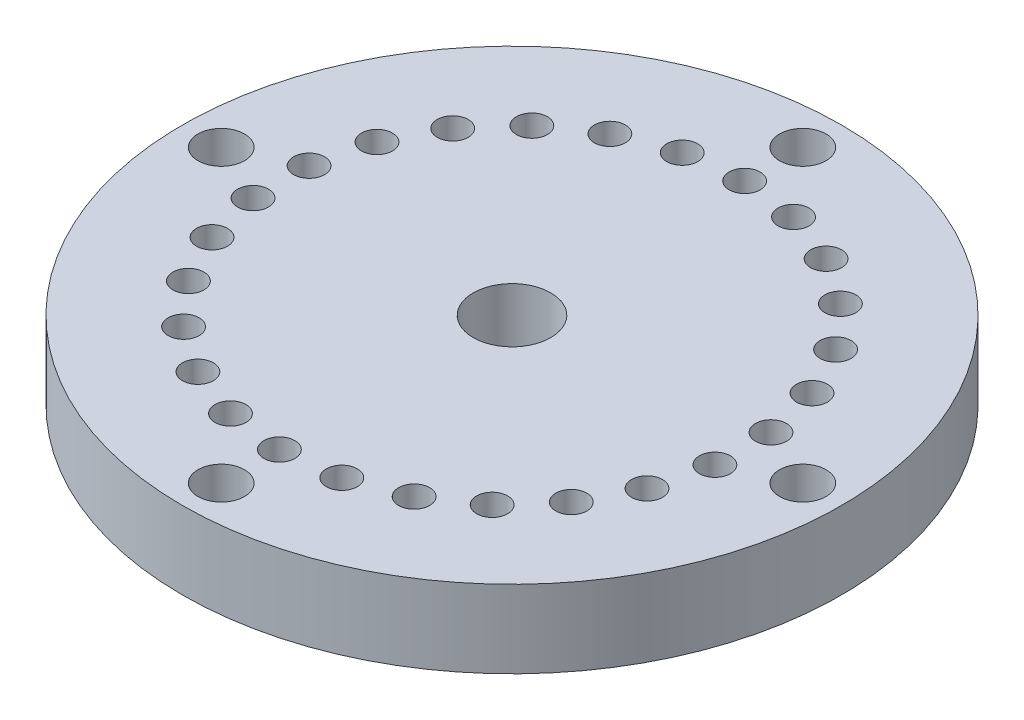
SolidWorks part; units mm, degrees
ref_plane "Plan de face" through (0, 0, 0) normal (0, 0, 1) x (1, 0, 0)
ref_plane "Plan de dessus" through (0, 0, 0) normal (0, 1, 0) x (1, 0, 0)
ref_plane "Plan de droite" through (0, 0, 0) normal (1, 0, 0) x (0, 0, -1)
sketch "Esquisse1" plane through (0, 0, 0) normal (0, 1, 0) x (1, 0, 0)
  circle A0 centre (0, 0) radius 4.25
  circle A1 centre (0, 0) radius 0.5
  circle A2 centre (0, 3) radius 0.2
  circle A3 centre (0, 3.75) radius 0.3
  circle A4 centre (0.7179, 2.9128) radius 0.2
  circle A5 centre (1.3942, 2.6564) radius 0.2
  circle A6 centre (1.9894, 2.2455) radius 0.2
  circle A7 centre (2.469, 1.7042) radius 0.2
  circle A8 centre (2.805, 1.0638) radius 0.2
  circle A9 centre (2.9781, 0.3616) radius 0.2
  circle A10 centre (2.9781, -0.3616) radius 0.2
  circle A11 centre (2.805, -1.0638) radius 0.2
  circle A12 centre (2.469, -1.7042) radius 0.2
  circle A13 centre (1.9894, -2.2455) radius 0.2
  circle A14 centre (1.3942, -2.6564) radius 0.2
  circle A15 centre (0.7179, -2.9128) radius 0.2
  circle A16 centre (0, -3) radius 0.2
  circle A17 centre (-0.7179, -2.9128) radius 0.2
  circle A18 centre (-1.3942, -2.6564) radius 0.2
  circle A19 centre (-1.9894, -2.2455) radius 0.2
  circle A20 centre (-2.469, -1.7042) radius 0.2
  circle A21 centre (-2.805, -1.0638) radius 0.2
  circle A22 centre (-2.9781, -0.3616) radius 0.2
  circle A23 centre (-2.9781, 0.3616) radius 0.2
  circle A24 centre (-2.805, 1.0638) radius 0.2
  circle A25 centre (-2.469, 1.7042) radius 0.2
  circle A26 centre (-1.9894, 2.2455) radius 0.2
  circle A27 centre (-1.3942, 2.6564) radius 0.2
  circle A28 centre (-0.7179, 2.9128) radius 0.2
  circle A29 centre (3.75, 0) radius 0.3
  circle A30 centre (0, -3.75) radius 0.3
  circle A31 centre (-3.75, 0) radius 0.3
  point P64 (0, 0)
  point P70 (0, 0)
  dimension "D1" = 8.5
  dimension "D2" = 1
  dimension "D3" = 3
  dimension "D4" = 3.75
  dimension "D5" = 26
extrude "Boss.-Extru.2" add sketch "Esquisse1" along normal blind 1
